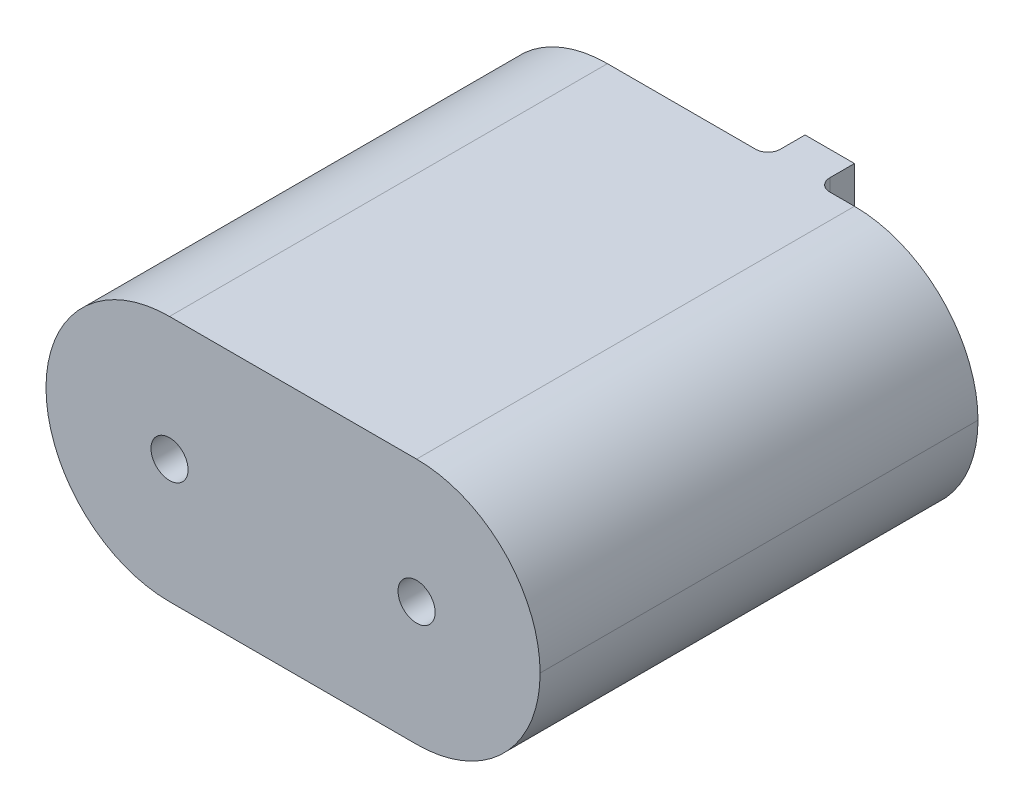
SolidWorks part; units mm, degrees
material "ABS PC"
ref_plane "前视基准面" through (0, 0, 0) normal (0, 0, 1) x (1, 0, 0)
ref_plane "上视基准面" through (0, 0, 0) normal (0, 1, 0) x (1, 0, 0)
ref_plane "右视基准面" through (0, 0, 0) normal (1, 0, 0) x (0, 0, -1)
other "Configuration Table"
sketch "草图1" plane through (0, 0, 0) normal (0, 1, 0) x (1, 0, 0)
  line L1 (-20, 17.725) -> (20, 17.725)
  line L2 (-20, 17.725) -> (-20, -17.725)
  line L3 (-20, -17.725) -> (20, -17.725)
  line L4 (20, 17.725) -> (20, -17.725)
  line L5 (-20, 17.725) -> (20, -17.725) construction
  line L6 (-20, -17.725) -> (20, 17.725) construction
  point P0 (0, 0)
  dimension "D1" = 35.45
  dimension "D2" = 40
extrude "凸台-拉伸1" add sketch "草图1" along normal blind 20
fillet "圆角1" radius 10 4 edges at (-20, 0, 0) (-20, 20, 0) (20, 0, 0) (20, 20, 0)
sketch "草图2" plane through (0, 0, -17.725) normal (0, 0, -1) x (-1, 0, 0)
  line L0 (0, 0) -> (0, 20) construction
  line L1 (-10, 20) -> (10, 20) construction
  circle A0 centre (-10, 10) radius 1.5
  circle A1 centre (10, 10) radius 1.5
  dimension "D1" = 3
extrude "切除-拉伸1" cut sketch "草图2" against normal blind 77
sketch "草图3" plane through (0, 0, -17.725) normal (0, 0, -1) x (-1, 0, 0)
  line L0 (-20, 10) -> (20, 10) construction
  line L1 (-5, 20) -> (-5, 0)
  line L2 (-10, 20) -> (10, 20) construction
  line L3 (-10, 0) -> (10, 0) construction
  line L4 (-7, 20) -> (-7, 0)
  line L5 (-3, 20) -> (-3, 0)
  line L8 (-10, 0) -> (10, 0)
  line L9 (10, 20) -> (-10, 20)
  line L10 (-10, 0) -> (10, 0)
  line L11 (10, 20) -> (-10, 20)
  arc A4 (10, 0) -> (20, 10) centre (10, 10) ccw
  arc A5 (20, 10) -> (10, 20) centre (10, 10) ccw
  arc A6 (-10, 20) -> (-20, 10) centre (-10, 10) ccw
  arc A7 (-20, 10) -> (-10, 0) centre (-10, 10) ccw
  arc A8 (10, 0) -> (20, 10) centre (10, 10) ccw
  arc A9 (20, 10) -> (10, 20) centre (10, 10) ccw
  arc A10 (-10, 20) -> (-20, 10) centre (-10, 10) ccw
  arc A11 (-20, 10) -> (-10, 0) centre (-10, 10) ccw
  line M11 (-10, 0) -> (10, 0)
  line M14 (10, 20) -> (-10, 20)
  dimension "D1" = 15
  dimension "D2" = 2
  dimension "D3" = 2
  dimension "D4" = 0
extrude "凸台-拉伸2" add sketch "草图3" along normal blind 3 contours L0 L4 L1 M11 | L4 L0 L1 M14 | L0 L1 L5 M11 | L1 L0 L5 M14 region at (6, 15, -17.725) region at (6, 5, -17.725) region at (4, 15, -17.725) region at (4, 5, -17.725)
sketch "草图4" plane through (0, 0, -20.725) normal (0, 0, -1) x (-1, 0, 0)
  line L0 (-7, 10) -> (17.8808, 10) construction
  line L1 (-7, 20) -> (-7, 0) construction
  line L3 (-13.7521, 15) -> (-0.2479, 15)
  line L4 (-13.7521, 15) -> (-13.7521, 5)
  line L5 (-13.7521, 5) -> (-0.2479, 5)
  line L6 (-0.2479, 15) -> (-0.2479, 5)
  line L7 (-13.7521, 15) -> (-0.2479, 5) construction
  line L8 (-13.7521, 5) -> (-0.2479, 15) construction
  dimension "D1" = 10
extrude "切除-拉伸2" cut sketch "草图4" against normal blind 3
fillet "圆角2" radius 1 4 edges at (3, 2.5, -17.725) (7, 2.5, -17.725) (7, 17.5, -17.725) (3, 17.5, -17.725)
